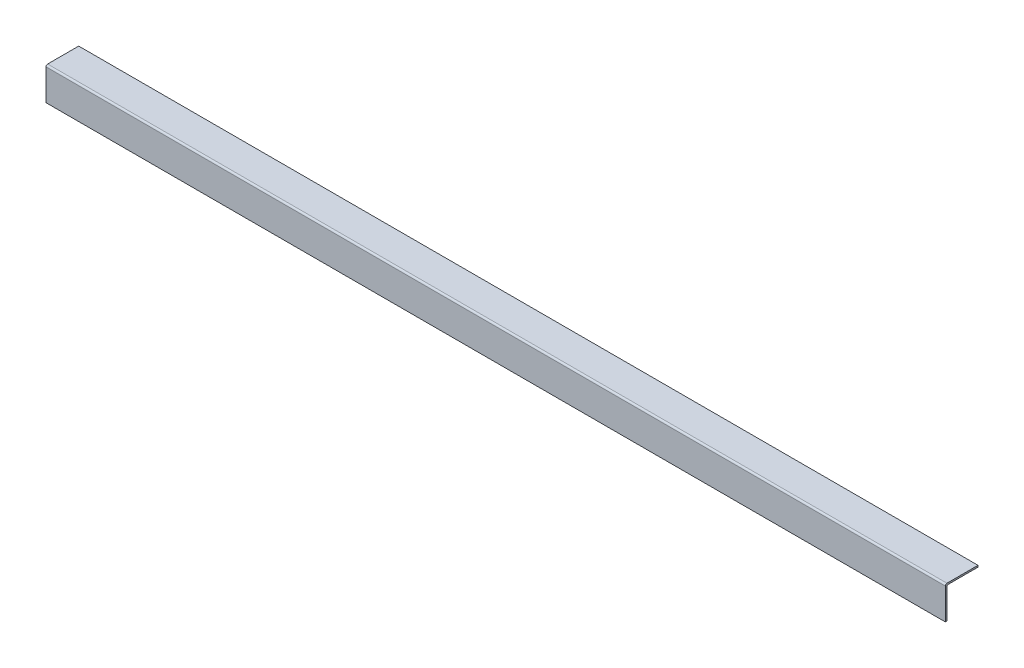
SolidWorks part; units mm, degrees
material "1060 Alloy"
ref_plane "Front Plane" through (0, 0, 0) normal (0, 0, 1) x (1, 0, 0)
ref_plane "Top Plane" through (0, 0, 0) normal (0, 1, 0) x (1, 0, 0)
ref_plane "Right Plane" through (0, 0, 0) normal (1, 0, 0) x (0, 0, -1)
sketch "Sketch1" plane through (0, 0, 0) normal (1, 0, 0) x (0, 0, -1)
  line L0 (0, -10) -> (0, -0.5)
  line L1 (0.5, 0) -> (10, 0)
  line L2 (10, 0) -> (10, -0.5)
  line L3 (10, -0.5) -> (1, -0.5)
  line L4 (0, -10) -> (0.5, -10)
  line L5 (0.5, -10) -> (0.5, -1)
  arc A0 (0, -0.5) -> (0.5, 0) centre (0.5, -0.5) cw
  arc A1 (1, -0.5) -> (0.5, -1) centre (1, -1) ccw
  point P10 (0, 0)
  dimension "D3" = 0.5
  dimension "D1" = 10
  dimension "D2" = 0.5
extrude "Boss-Extrude1" add sketch "Sketch1" along normal blind 137.5 and the other way blind 137.5
